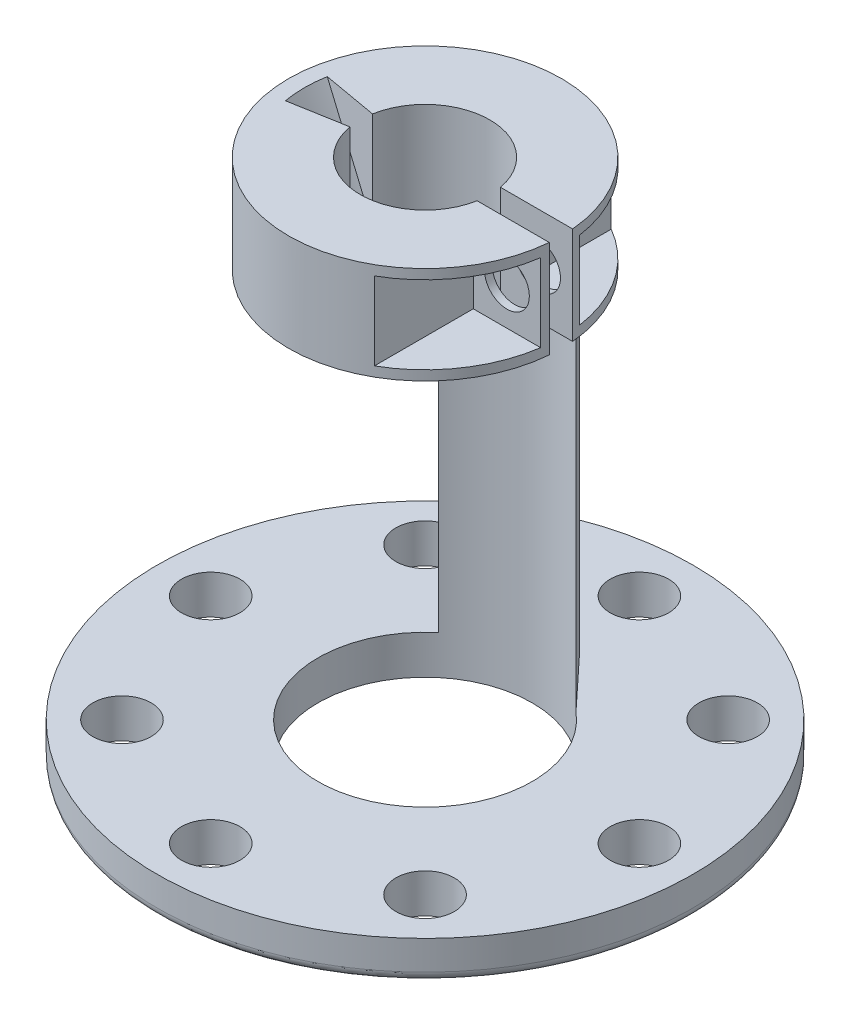
SolidWorks part; units mm, degrees
material "AISI 1035 Acier (SS)"
ref_plane "Plan de face" through (0, 0, 0) normal (0, 0, 1) x (1, 0, 0)
ref_plane "Plan de dessus" through (0, 0, 0) normal (0, 1, 0) x (1, 0, 0)
ref_plane "Plan de droite" through (0, 0, 0) normal (1, 0, 0) x (0, 0, -1)
sketch "Esquisse1" plane through (0, 0, 0) normal (0, 0, 1) x (1, 0, 0)
  line L2 (13.75, 2) -> (13.75, 0)
  line L11 (13.75, 0) -> (5.5, 0)
  line L12 (0, 0) -> (0, 15) construction
  line L16 (5.5, 0) -> (5.5, 2)
  line L17 (5.5, 2) -> (13.75, 2)
  dimension "D1" = 5.5
  dimension "D2" = 2
  dimension "D5" = 13.75
revolve "Révolution2" add sketch "Esquisse1" angle 360 about L12
fillet "Congé1" radius 0.5 1 edges at (0, 0, -13.75)
sketch "Esquisse8" plane through (0, 2, 0) normal (0, 1, 0) x (1, 0, 0)
  circle A0 centre (11, 0) radius 1.5
  point P12 (0, 0)
  dimension "D1" = 1.5
  dimension "D2" = 11
extrude "Enlèv. mat.-Extru.2" cut sketch "Esquisse8" against normal through all
pattern_circular "Répétition circulaire2" count 8 over 360 about axis through (0, 0, 0) along (0, -1, 0) of "Enlèv. mat.-Extru.2" reverse direction yes
sketch "Esquisse9" plane through (0, 2, 0) normal (0, 1, 0) x (1, 0, 0)
  line L0 (-3.5222, 4.2242) -> (-1, 6.9282)
  line L1 (3.5222, 4.2242) -> (1, 6.9282)
  arc A0 (-3.5222, 4.2242) -> (3.5222, 4.2242) centre (0, 0) cw
  arc A2 (-1, 6.9282) -> (1, 6.9282) centre (0, 0) cw
  circle A3 centre (0, 0) radius 5.5 construction
  dimension "D3" = 3.6977
  dimension "D1" = 7
  dimension "D4" = 3.6977
  dimension "D2" = 1
extrude "Boss.-Extru.1" add sketch "Esquisse9" along normal blind 20
sketch "Esquisse11" plane through (0, 22, 0) normal (0, 1, 0) x (1, 0, 0)
  circle A0 centre (0, 0) radius 7
  arc A1 (1, 6.9282) -> (-1, 6.9282) centre (0, 0) ccw construction
  circle A4 centre (0, 0) radius 3.325
  dimension "D1" = 6.65
extrude "Boss.-Extru.2" add sketch "Esquisse11" along normal blind 5
sketch "Esquisse12" plane through (0, 27, 0) normal (0, 1, 0) x (1, 0, 0)
  line L1 (2.9255, 0.6) -> (7.9255, 0.6)
  line L2 (2.9255, 0.6) -> (2.9255, -0.6)
  line L3 (2.9255, -0.6) -> (7.9255, -0.6)
  line L4 (7.9255, 0.6) -> (7.9255, -0.6)
  dimension "D1" = 2.9255
  dimension "D2" = 0.6
  dimension "D3" = 0.6
  dimension "D4" = 5
extrude "Enlèv. mat.-Extru.3" cut sketch "Esquisse12" against normal up to next
sketch "Esquisse13" plane through (0, 27, 0) normal (0, 1, 0) x (1, 0, 0)
  arc A0 (1, 6.9282) -> (-1, 6.9282) centre (0, 0) ccw construction
  circle A1 centre (0, 0) radius 7 construction
  point P0 (0, 7)
  point P1 (0, -7)
ref_plane "Plan1" through (0, 27, 7) normal (0, 0, 1) x (1, 0, 0)
sketch "Esquisse14" plane through (0, 27, 7) normal (0, 0, 1) x (1, 0, 0)
  line L0 (6.9742, -0.5) -> (3.4742, -0.5)
  line L1 (6.9742, 0) -> (6.9742, -5) construction
  line L2 (3.4742, -0.5) -> (3.4742, -4.5)
  line L3 (3.4742, -4.5) -> (6.9742, -4.5)
  line L4 (6.9742, -4.5) -> (6.9742, -0.5)
  line L5 (3.2704, 0) -> (6.9742, 0) construction
  dimension "D1" = 4
  dimension "D2" = 0.5
  dimension "D3" = 3.5
extrude "Enlèv. mat.-Extru.5" cut sketch "Esquisse14" against normal blind 6
sketch "Esquisse16" plane through (0, 0, 1) normal (0, 0, 1) x (1, 0, 0)
  line L0 (3.4742, 22.5) -> (6.9282, 22.5) construction
  line L1 (3.4742, 22.5) -> (3.4742, 26.5) construction
  circle A0 centre (5.2012, 24.5) radius 1.15
  point P4 (5.2012, 22.5)
  point P7 (3.4742, 24.5)
  dimension "D1" = 2.3
extrude "Enlèv. mat.-Extru.6" cut sketch "Esquisse16" against normal blind 6
mirror "Symétrie1" about plane through (0, 0, 0) normal (0, 0, 1) of "Enlèv. mat.-Extru.5"
sketch "Esquisse17" plane through (0, 0, 0) normal (0, 0, 1) x (1, 0, 0)
  line L0 (-6.1878, 27) -> (-3.325, 22)
  line L1 (6.9742, 27) -> (-7, 27) construction
  line L2 (-3.325, 22) -> (-3.325, 27)
  line L3 (-3.325, 27) -> (-6.1878, 27)
  line L4 (0, 0) -> (0, 27) construction
  line L5 (-13.25, 0) -> (13.25, 0) construction
  point P7 (0, 0)
  point P11 (-3.325, 22)
revolve "Enlèvement de matière-Révolution1" cut sketch "Esquisse17" angle 20 mid plane about L4
